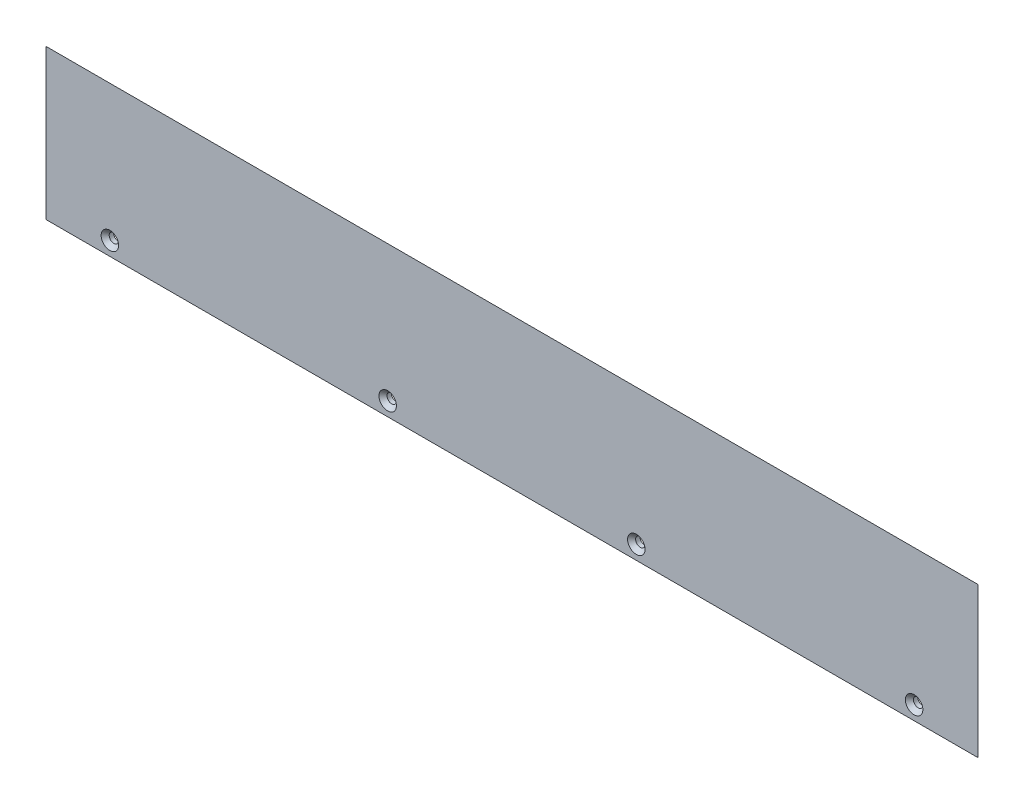
SolidWorks part; units mm, degrees
ref_plane "Front Plane" through (0, 0, 0) normal (0, 0, 1) x (1, 0, 0)
ref_plane "Top Plane" through (0, 0, 0) normal (0, 1, 0) x (1, 0, 0)
ref_plane "Right Plane" through (0, 0, 0) normal (1, 0, 0) x (0, 0, -1)
sketch "Sketch1" plane through (0, 0, 0) normal (0, 0, 1) x (1, 0, 0)
  line L1 (0, 0) -> (335.5, 0)
  line L2 (0, 0) -> (0, 54)
  line L3 (0, 54) -> (335.5, 54)
  line L4 (335.5, 0) -> (335.5, 54)
  dimension "D1" = 54
  dimension "D2" = 335.5
extrude "Boss-Extrude1" add sketch "Sketch1" along normal blind 3
chamfer "Chamfer1" distance 3 angle 45 3 edges at (0, 27, 0) (167.75, 54, 0) (335.5, 27, 0)
sketch "Sketch2" plane through (0, 0, 3) normal (0, 0, 1) x (1, 0, 0)
  line L0 (0, 5) -> (335.5, 5) construction
  line L1 (0, 54) -> (0, 0) construction
  line L2 (335.5, 0) -> (335.5, 54) construction
  line L3 (0, 0) -> (335.5, 0) construction
  circle A0 centre (23, 5) radius 1.5
  circle A1 centre (123, 5) radius 1.5
  circle A2 centre (212.5, 5) radius 1.5
  circle A3 centre (312.5, 5) radius 1.5
  dimension "D6" = 3
  dimension "D1" = 5
  dimension "D2" = 23
  dimension "D3" = 100
  dimension "D4" = 100
  dimension "D5" = 23
hole_wizard "CSK for M3 Flat Head Machine Screw1" positions "Sketch4" profile "Sketch3" countersink size "M3" standard "ANSI Metric" end condition through all
sketch "Sketch4" plane through (0, 0, 3) normal (0, 0, 1) x (1, 0, 0)
  point P0 (23, 5)
  point P3 (123, 5)
  point P6 (212.5, 5)
  point P9 (312.5, 5)
sketch "Sketch3" plane through (23, 5, 3) normal (1, 0, 0) x (0, -1, 0)
  line L0 (0, 0) -> (0, 3)
  line L1 (0, 3) -> (1.7, 3)
  line L2 (1.7, 3) -> (1.7, 1.45)
  line L3 (1.7, 1.45) -> (3.15, 0)
  line L5 (3.15, 0) -> (0, 0)
  line L6 (-1.7, 1.45) -> (-3.15, 0) construction
  line L11 (0, -6.35) -> (0, 107.95) construction
  dimension "Thru Hole Dia." = 3.4
  dimension "Thru Hole Depth" = 3
  dimension "Near C'Sink Dia." = 6.3
  dimension "Near C'Sink Angle" = 90
